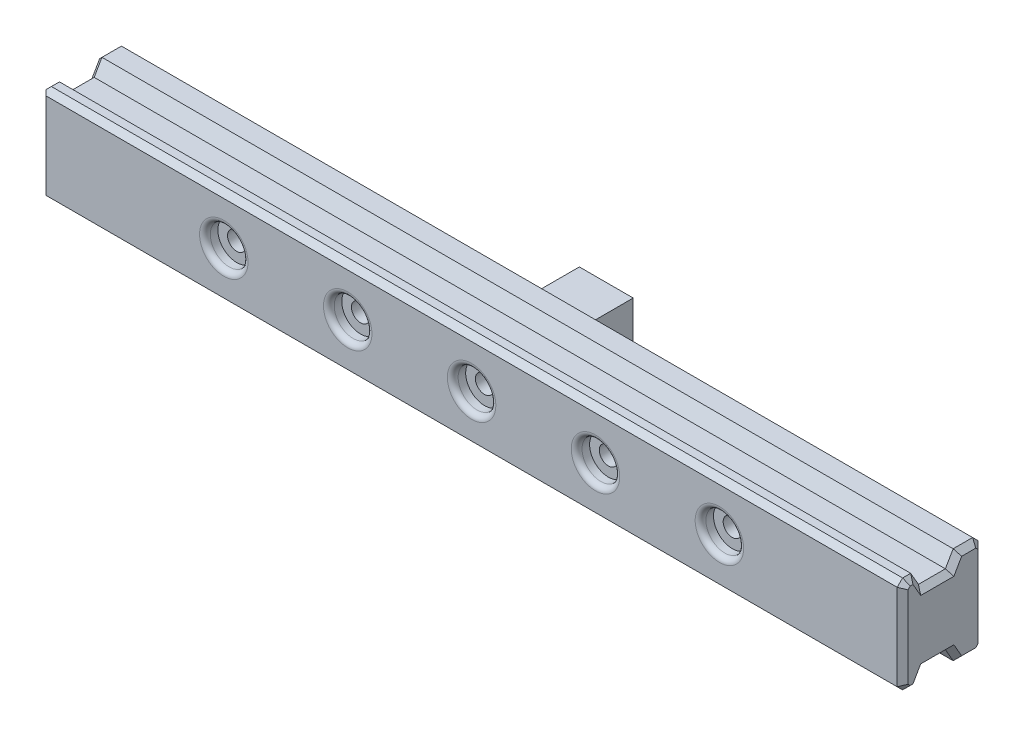
SolidWorks part; units mm, degrees
ref_plane "Płaszczyzna przednia" through (0, 0, 0) normal (0, 0, 1) x (1, 0, 0)
ref_plane "Płaszczyzna górna" through (0, 0, 0) normal (0, 1, 0) x (1, 0, 0)
ref_plane "Płaszczyzna prawa" through (0, 0, 0) normal (1, 0, 0) x (0, 0, -1)
sketch "Szkic1" plane through (0, 0, 0) normal (0, 0, 1) x (1, 0, 0)
  line L1 (-80, 9) -> (80, 9)
  line L2 (-80, 9) -> (-80, -9)
  line L3 (-80, -9) -> (80, -9)
  line L4 (80, 9) -> (80, -9)
  line L5 (-80, 9) -> (80, -9) construction
  line L6 (-80, -9) -> (80, 9) construction
  point P0 (0, 0)
  dimension "D1" = 160
  dimension "D2" = 18
extrude "Dodanie-wyciągnięcie1" add sketch "Szkic1" along normal blind 15
sketch "Szkic2" plane through (80, 0, 0) normal (1, 0, 0) x (0, 0, -1)
  line L1 (-15, 9) -> (0, 9) construction
  line L2 (-12.5, 9) -> (-11.0566, 6.5)
  line L3 (-11.0566, 6.5) -> (-6.0566, 6.5)
  line L4 (-6.0566, 6.5) -> (-4.6132, 9)
  line L5 (-4.6132, 9) -> (-12.5, 9)
  line L6 (-12.5, 9) -> (-12.5, -9) construction
  line L7 (-15, -9) -> (0, -9) construction
  line L8 (-4.6132, 9) -> (-4.6132, -2.1585) construction
  line L9 (0, 0) -> (-3.0897, 0) construction
  line L10 (-4.6132, -9) -> (-12.5, -9)
  line L11 (-6.0566, -6.5) -> (-4.6132, -9)
  line L12 (-11.0566, -6.5) -> (-6.0566, -6.5)
  line L13 (-12.5, -9) -> (-11.0566, -6.5)
  dimension "D1" = 2.5
  dimension "D2" = 30
  dimension "D4" = 30
  dimension "D5" = 5
extrude "Wytnij-wyciągnięcie1" cut sketch "Szkic2" against normal up to next
chamfer "Sfazowanie1" distance 1 angle 45 4 edges at (0, -9, 0) (0, 9, 0) (0, -9, 15) (0, 9, 15)
sketch "Szkic4" plane through (0, 0, 0) normal (0, 0, -1) x (-1, 0, 0)
  line L1 (-5, 5) -> (5, 5)
  line L2 (-5, 5) -> (-5, -5)
  line L3 (-5, -5) -> (5, -5)
  line L4 (5, 5) -> (5, -5)
  line L5 (-5, 5) -> (5, -5) construction
  line L6 (-5, -5) -> (5, 5) construction
  point P0 (0, 0)
  dimension "D1" = 10
  dimension "D2" = 10
extrude "Dodanie-wyciągnięcie2" add sketch "Szkic4" along normal blind 10
chamfer "Sfazowanie2" distance 1 angle 45 28 edges at (80, -7.75, 5.3349) (80, -6.5, 8.5566) (80, -7.75, 11.7783) (80, -9, 13.25) (80, -8.5, 14.5) (80, 0, 15) (80, 8.5, 14.5) (80, 9, 13.25) (80, 7.75, 11.7783) (80, 6.5, 8.5566) (80, 7.75, 5.3349) (80, 9, 2.8066) (80, 8.5, 0.5) (80, 0, 0) (80, -8.5, 0.5) (80, -9, 2.8066) (-80, -9, 13.25) (-80, -7.75, 11.7783) (-80, -6.5, 8.5566) (-80, -7.75, 5.3349) (-80, -9, 2.8066) (-80, 9, 13.25) (-80, 9, 2.8066) (-80, 7.75, 11.7783) (-80, 7.75, 5.3349) (-80, 6.5, 8.5566) (-80, 0, 15) (-80, 0, 0)
sketch "Szkic5" plane through (0, 0, 15) normal (0, 0, 1) x (1, 0, 0)
  point P0 (0, 0)
hole_wizard "Pogłębienie walcowe pod M3 Śrubę z łbem stożkowym ściętym1" positions "Szkic 3D2" profile "Szkic7" counterbore size "M3" standard "ISO" end condition up to next
sketch3d "Szkic 3D2"
  point P0 (0, 0, 15)
sketch "Szkic7" plane through (0, 0, 15) normal (1, 0, 0) x (0, -1, 0)
  line L0 (0, 0) -> (0, 25)
  line L1 (0, 25) -> (1.7, 25)
  line L3 (1.7, 25) -> (1.7, 2.4)
  line L4 (1.7, 2.4) -> (3.5, 2.4)
  line L5 (3.5, 2.4) -> (3.5, 0)
  line L7 (3.5, 0) -> (0, 0)
  line L11 (0, -6.35) -> (0, 107.95) construction
  dimension "Średnica otworu na wylot" = 3.4
  dimension "Głębokość otworu na wylot" = 25
  dimension "Średnica pogłębienia walcowego" = 7
  dimension "Głębokość pogłębienia walcowego" = 2.4
pattern_linear "Szyk liniowy1" count 3 spacing 23 along (1, 0, 0) of "Pogłębienie walcowe pod M3 Śrubę z łbem stożkowym ściętym1"
pattern_linear "Szyk liniowy2" count 3 spacing 23 along (-1, 0, 0) of "Szyk liniowy1"
fillet "Zaokrąglenie1" radius 1 5 edges at (49.5, 0, 15) (26.5, 0, 15) (3.5, 0, 15) (-19.5, 0, 15) (-42.5, 0, 15)
